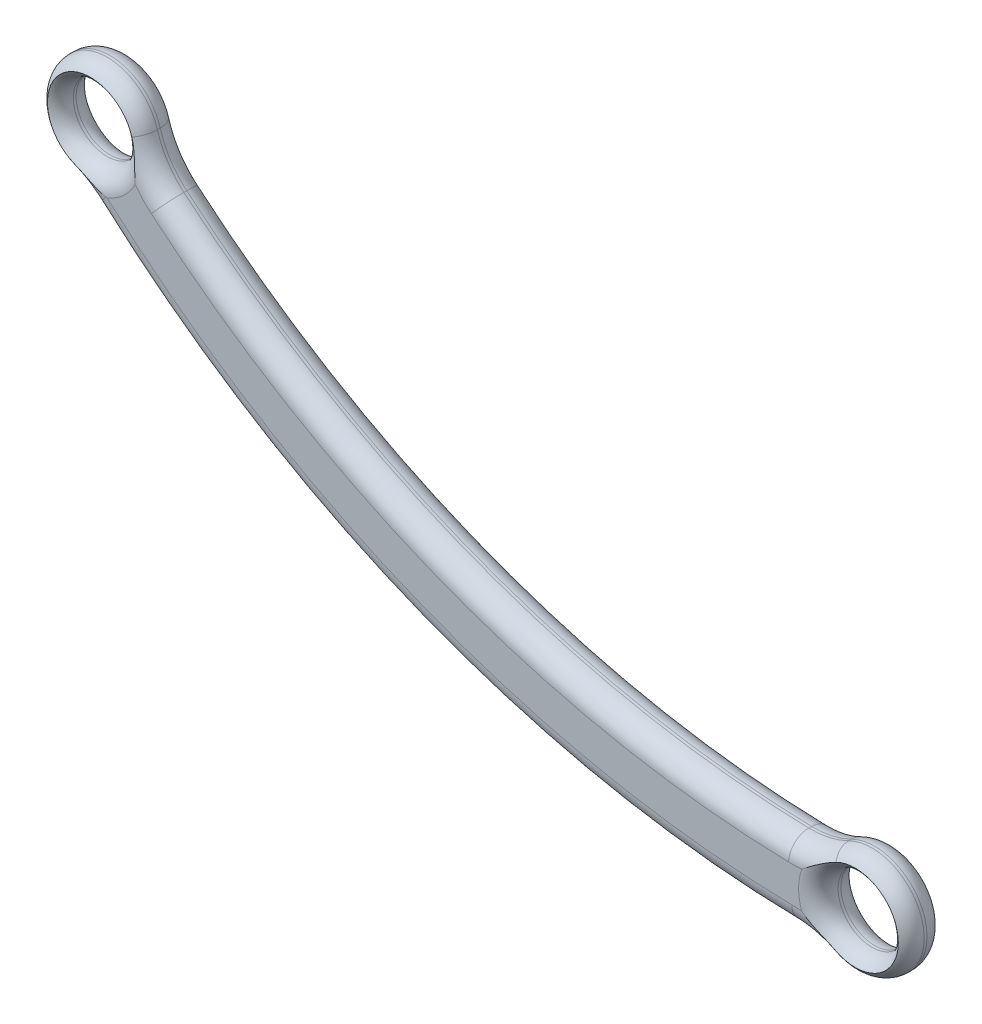
SolidWorks part; units mm, degrees
ref_plane "Front Plane" through (0, 0, 0) normal (0, 0, 1) x (1, 0, 0)
ref_plane "Top Plane" through (0, 0, 0) normal (0, 1, 0) x (1, 0, 0)
ref_plane "Right Plane" through (0, 0, 0) normal (1, 0, 0) x (0, 0, -1)
sketch "Sketch1" plane through (0, 0, 0) normal (0, 0, 1) x (1, 0, 0)
  line L0 (0, 0) -> (32.8847, 0) construction
  line L1 (0, 0) -> (-26.3159, 21.5473) construction
  line L2 (0, 0) -> (24.6472, 67.7177) construction
  line L3 (-26.3159, 21.5473) -> (32.8847, 0) construction
  arc A0 (-20.1889, 18.4244) -> (27.7437, 0) centre (27.4961, 70.9185) ccw
  arc A1 (-24.4347, 15.1114) -> (27.7334, -5.3126) centre (27.4961, 70.9185) ccw
  arc A2 (27.7334, -5.3126) -> (27.7437, 0) centre (30.3142, -2.6613) ccw
  arc A3 (-20.1889, 18.4244) -> (-24.4347, 15.1114) centre (-23.8729, 18.7685) ccw
  circle A4 centre (-23.8729, 18.7685) radius 2.4
  circle A5 centre (30.3142, -2.6613) radius 2.4
  point P8 (27.5829, 0)
  point P15 (27.7071, 0.2505)
  point P16 (-20.3877, 18.2303)
  point P17 (28.1702, -5.5551)
  point P18 (-24.7319, 14.8092)
  point P19 (-20.0687, 18.0239)
  point P20 (27.7437, -5.3126)
  point P21 (-24.4347, 15.1114)
  dimension "D3" = 4.8
  dimension "D4" = 4.8
  dimension "D5" = 3.7
  dimension "D6" = 3.7
  dimension "D1" = 20
  dimension "D2" = 63
extrude "Boss-Extrude1" add sketch "Sketch1" along normal blind 3
fillet "Fillet1" radius 6 4 edges at (-20.1889, 18.4244, 1.5) (-24.4347, 15.1114, 1.5) (27.7334, -5.3126, 1.5) (27.7437, 0, 1.5)
fillet "Fillet2" radius 1.4 20 edges at (32.7142, -2.6613, 0) (-21.4729, 18.7685, 0) (-24.3076, 14.8577, 0) (-0.4838, 0.0075, 0) (27.3592, -5.4782, 0) (34.0142, -2.6792, 0) (27.29, 0.1617, 0) (2.2504, 4.6452, 0) (-19.593, 18.2023, 0) (-26.3556, 21.5119, 0) (32.7142, -2.6613, 3) (27.29, 0.1617, 3) (34.0142, -2.6792, 3) (27.3592, -5.4782, 3) (-0.4838, 0.0075, 3) (-24.3076, 14.8577, 3) (-26.3556, 21.5119, 3) (-19.593, 18.2023, 3) (2.2504, 4.6452, 3) (-21.4729, 18.7685, 3)
scale "Scale1" scale about centroid uniform scaling yes scale factor 1.15
